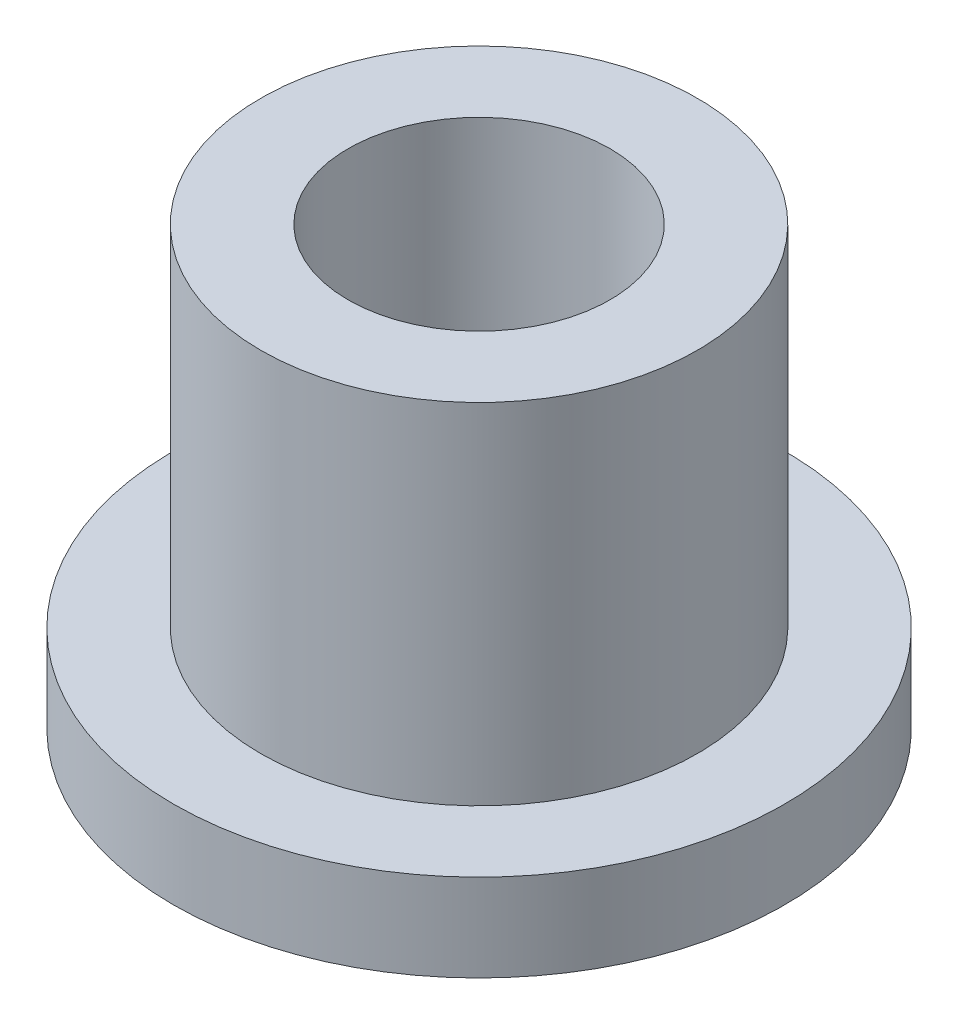
SolidWorks part; units mm, degrees
ref_plane "Front" through (0, 0, 0) normal (0, 0, 1) x (1, 0, 0)
ref_plane "Top" through (0, 0, 0) normal (0, 1, 0) x (1, 0, 0)
ref_plane "Right" through (0, 0, 0) normal (1, 0, 0) x (0, 0, -1)
sketch "Sketch1" plane through (0, 0, 0) normal (0, 1, 0) x (1, 0, 0)
  circle A0 centre (0, 0) radius 3
  circle A1 centre (0, 0) radius 5
  circle A2 centre (0, 0) radius 7
  dimension "ID" = 6
  dimension "OD" = 10
  dimension "FlangeOD" = 14
sketch "Sketch2" plane through (0, 0, 0) normal (0, 1, 0) x (1, 0, 0)
  circle A0 centre (0, 0) radius 3 construction
  circle A1 centre (0, 0) radius 5 construction
  circle A2 centre (0, 0) radius 3
  circle A3 centre (0, 0) radius 5
extrude "Boss-Extrude1" add sketch "Sketch2" along normal blind 10
sketch "Sketch3" plane through (0, 0, 0) normal (0, 1, 0) x (1, 0, 0)
  circle A0 centre (0, 0) radius 7 construction
  circle A1 centre (0, 0) radius 5 construction
  circle A2 centre (0, 0) radius 7
  circle A3 centre (0, 0) radius 5
extrude "Boss-Extrude2" add sketch "Sketch3" along normal blind 2
ref_axis "Center Axis 1" through (0, 10, 0) along (0, -1, 0)
ref_plane "Contact Plane 1" through (0, 10, 0) normal (0, 1, 0) x (1, 0, 0)
ref_plane "Contact Plane 2" through (0, 0, 0) normal (0, -1, 0) x (-1, 0, 0)
